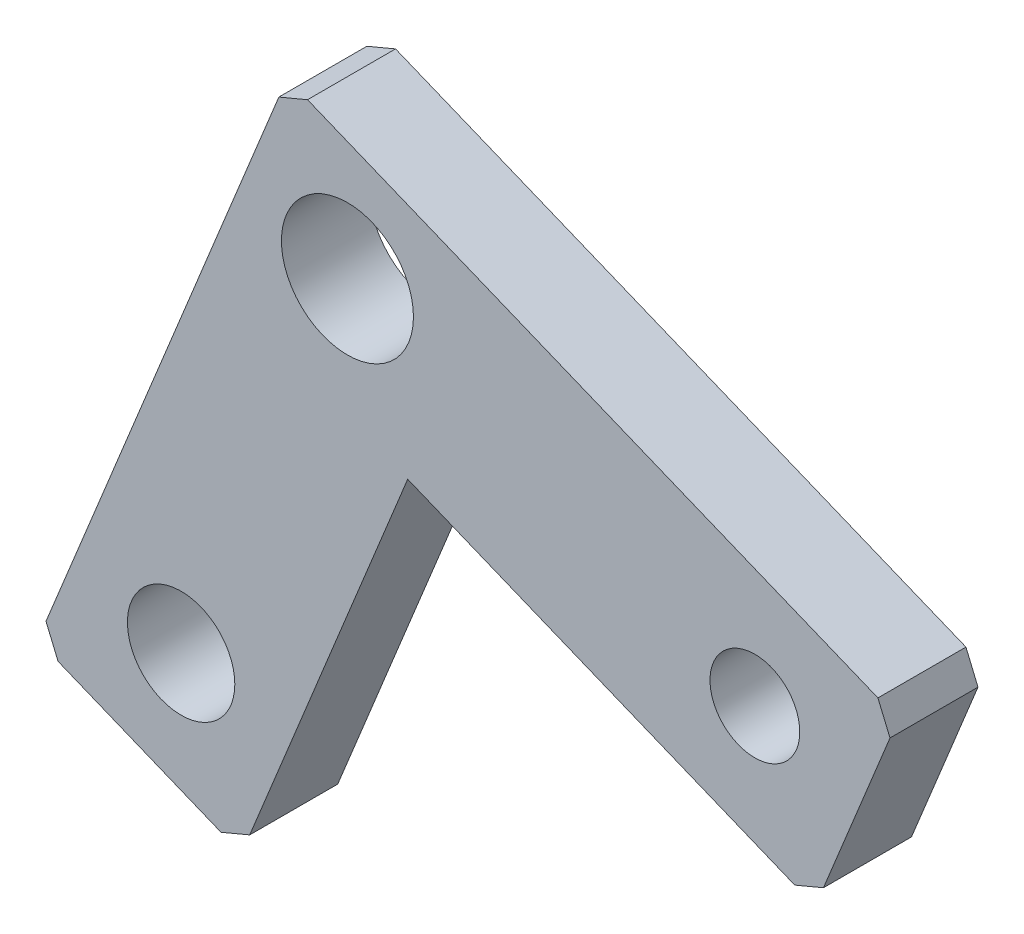
SolidWorks part; units mm, degrees
ref_plane "前基準面" through (0, 0, 0) normal (0, 0, 1) x (1, 0, 0)
ref_plane "上基準面" through (0, 0, 0) normal (0, 1, 0) x (1, 0, 0)
ref_plane "右基準面" through (0, 0, 0) normal (1, 0, 0) x (0, 0, -1)
sketch "草圖1" plane through (0, 0, 0) normal (0, 0, 1) x (1, 0, 0)
  line L0 (-42.6847, 14.9509) -> (26.7532, -13.3931)
  line L5 (26.7532, -13.3931) -> (17.3052, -36.5391)
  line L6 (17.3052, -36.5391) -> (-28.9867, -17.6431)
  line L7 (-28.9867, -17.6431) -> (-47.8827, -63.935)
  line L8 (-47.8827, -63.935) -> (-71.0287, -54.487)
  line L9 (-71.0287, -54.487) -> (-42.6847, 14.9509)
  line L10 (22.0292, -24.9661) -> (-47.4087, 3.3779) construction
  line L11 (-59.4557, -59.211) -> (-31.1117, 10.2269) construction
  circle A0 centre (10.4562, -20.2421) radius 5.1
  circle A1 centre (-35.8357, -1.3461) radius 7.5
  circle A2 centre (-54.7317, -47.638) radius 6.1
  point P12 (-35.8357, -1.3461)
  dimension "D5" = 10.2
  dimension "D8" = 15
  dimension "D9" = 12.2
  dimension "D1" = 25
  dimension "D2" = 25
  dimension "D3" = 75
  dimension "D4" = 75
  dimension "D6" = 12.5
  dimension "D7" = 12.5
  dimension "D10" = 12.5
extrude "填料-伸長1" add sketch "草圖1" against normal blind 10
chamfer "導角1" distance 2.5 angle 45 5 edges at (-47.8827, -63.935, -5) (17.3052, -36.5391, -5) (26.7532, -13.3931, -5) (-71.0287, -54.487, -5) (-42.6847, 14.9509, -5)
